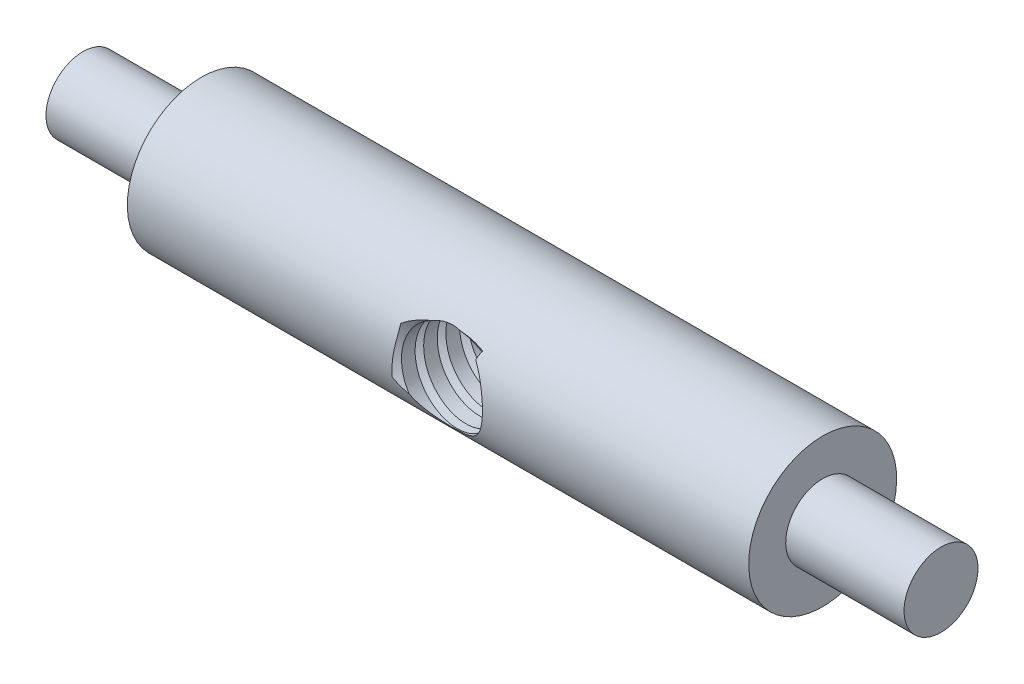
SolidWorks part; units mm, degrees
ref_plane "前基準面" through (0, 0, 0) normal (0, 0, 1) x (1, 0, 0)
ref_plane "上基準面" through (0, 0, 0) normal (0, 1, 0) x (1, 0, 0)
ref_plane "右基準面" through (0, 0, 0) normal (1, 0, 0) x (0, 0, -1)
sketch "草圖1" plane through (0, 0, 0) normal (0, 0, 1) x (1, 0, 0)
  line L0 (-29, 0) -> (-29, 2.5)
  line L1 (-29, 2.5) -> (-21, 2.5)
  line L2 (-21, 2.5) -> (-21, 5)
  line L3 (-21, 5) -> (21, 5)
  line L4 (21, 5) -> (21, 2.5)
  line L5 (21, 2.5) -> (29, 2.5)
  line L6 (29, 2.5) -> (29, 0)
  line L7 (29, 0) -> (-29, 0)
  dimension "D1" = 2.5
  dimension "D2" = 8
  dimension "D3" = 5
  dimension "D4" = 0
  dimension "D5" = 42
  dimension "D6" = 21
revolve "旋轉1" add sketch "草圖1" angle 360 about L7
sketch "草圖3" plane through (0, 0, 0) normal (0, 0, 1) x (1, 0, 0)
  circle A0 centre (0, 0) radius 3
  dimension "D1" = 6
extrude "除料-伸長1" cut sketch "草圖3" against normal mid plane 20
ref_plane "平面1" through (0, 0, 7) normal (0, 0, 1) x (1, 0, 0)
sketch "草圖16" plane through (0, 0, 7) normal (0, 0, 1) x (1, 0, 0)
  circle A0 centre (0, 0) radius 3.5
  dimension "D1" = 7
curve "螺旋曲線/渦捲線2" pitch 1.5 height 15 radius 3.5 centre (0, 0, 7) axis (0, 0, -1) start towards (1, 0, 0)
sketch "草圖17" plane through (0, 0, 0) normal (0, 1, 0) x (1, 0, 0)
  line L4 (3.5, -7) -> (1.7679, -6)
  line L5 (1.7679, -6) -> (1.7679, -8)
  line L6 (1.7679, -8) -> (3.5, -7)
  circle A0 centre (2.3453, -7) radius 0.5774 construction
  dimension "D1" = 2
sweep "除料-掃出6" cut profiles "草圖17" path "螺旋曲線/渦捲線2" align with end faces yes
